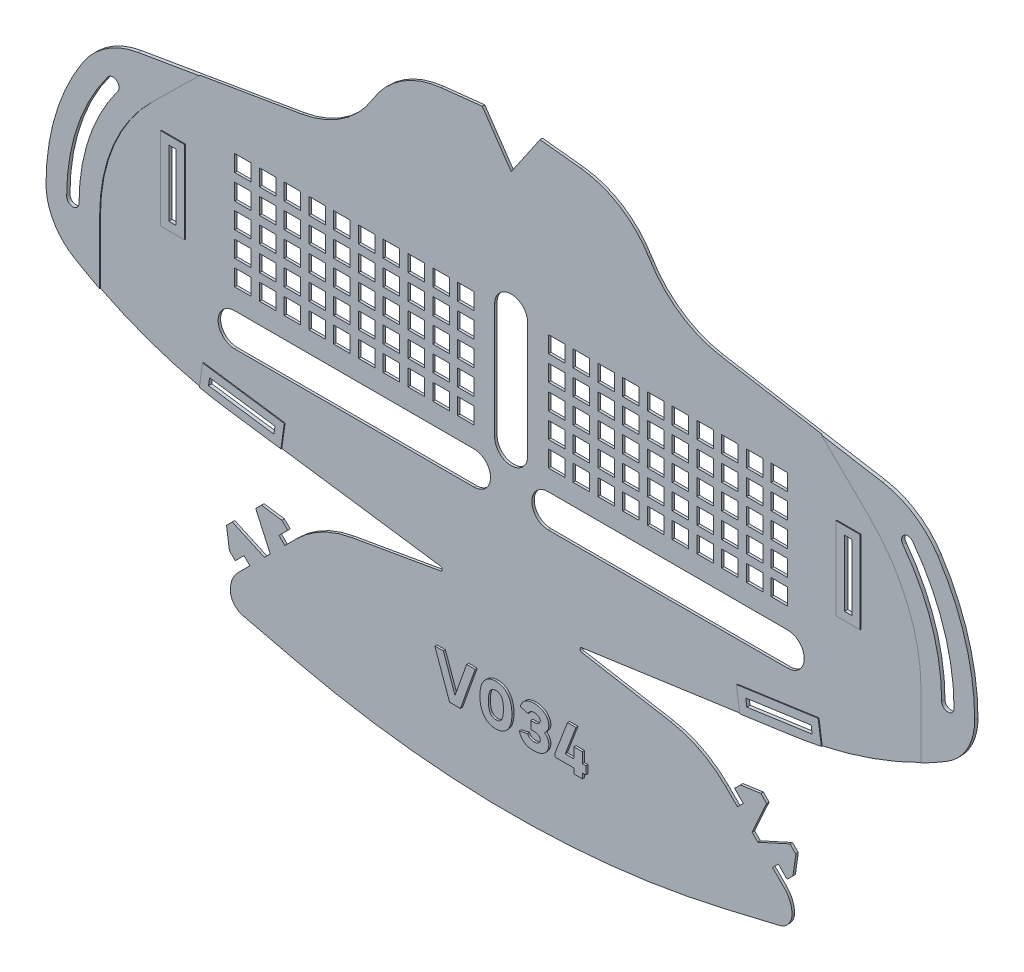
SolidWorks part; units mm, degrees
ref_plane "Front Plane" through (0, 0, 0) normal (0, 0, 1) x (1, 0, 0)
ref_plane "Top Plane" through (0, 0, 0) normal (0, 1, 0) x (1, 0, 0)
ref_plane "Right Plane" through (0, 0, 0) normal (1, 0, 0) x (0, 0, -1)
sketch "Sketch1" plane through (0, 0, 0) normal (0, 0, 1) x (1, 0, 0)
  line L0 (0, 0) -> (0, -145) construction
  line L1 (-14, -102) -> (14, -102) construction
  line L2 (-112.5, -69) -> (112.5, -69) construction
  line L3 (0, -10.2352) -> (-7, 0)
  line L4 (0, -10.2352) -> (7, 0)
  line L5 (7, 0) -> (16.9419, -1.0768)
  line L6 (-90.1804, -30.1909) -> (-50.7439, -23.5)
  line L7 (90.1804, -30.1909) -> (50.7439, -23.5)
  line L8 (-14, -102) -> (-68.2662, -94.2919)
  line L9 (-7, 0) -> (-16.9419, -1.0768)
  line L10 (14, -102) -> (68.2662, -94.2919)
  line L11 (-103.5977, -39) -> (-103.5977, -69) construction
  line L12 (-14, -102) -> (-38.6266, -106.305)
  line L13 (-52, -113.2546) -> (-54.8283, -116.0832)
  line L14 (52, -113.2546) -> (54.8283, -116.0832)
  line L15 (14, -102) -> (38.6266, -106.305)
  line L16 (-54.8283, -116.0832) -> (-56.2426, -114.669)
  line L17 (-56.2426, -114.669) -> (-54.1214, -112.5476)
  line L18 (-54.1214, -112.5476) -> (-55.5356, -111.1334)
  line L19 (-55.5356, -111.1334) -> (-60.4854, -110.4265)
  line L20 (-60.4854, -110.4265) -> (-68.9703, -118.9122)
  line L21 (-64.7275, -123.1546) -> (-63.3132, -124.5688)
  line L22 (-63.3132, -124.5688) -> (-66.1415, -127.3973)
  line L23 (-64.7275, -123.1546) -> (-66.8487, -125.2761)
  line L24 (-66.8487, -125.2761) -> (-68.263, -123.8619)
  line L25 (-68.9703, -118.9122) -> (-68.263, -123.8619)
  line L26 (68.9703, -118.9122) -> (68.263, -123.8619)
  line L27 (66.8487, -125.2761) -> (68.263, -123.8619)
  line L28 (64.7275, -123.1546) -> (66.8487, -125.2761)
  line L29 (63.3132, -124.5688) -> (66.1415, -127.3973)
  line L30 (64.7275, -123.1546) -> (63.3132, -124.5688)
  line L31 (60.4854, -110.4265) -> (68.9703, -118.9122)
  line L32 (55.5356, -111.1334) -> (60.4854, -110.4265)
  line L33 (54.1214, -112.5476) -> (55.5356, -111.1334)
  line L34 (56.2426, -114.669) -> (54.1214, -112.5476)
  line L35 (54.8283, -116.0832) -> (56.2426, -114.669)
  line L36 (-64.9691, -135.8852) -> (-52.4361, -138.8607)
  line L37 (64.9691, -135.8852) -> (52.4361, -138.8607)
  line L38 (-68.9703, -118.9122) -> (-64.7275, -123.1546) construction
  line L39 (-60.4854, -110.4265) -> (-56.2426, -114.669) construction
  arc A0 (-16.9419, -1.0768) -> (-33.4614, -11.6696) centre (-14.5729, -22.9489) ccw
  arc A1 (-33.4614, -11.6696) -> (-50.7439, -23.5) centre (-54.9257, 1.1478) cw
  arc A2 (-103.5977, -39) -> (-90.1804, -30.1909) centre (-86.8349, -49.9091) cw
  arc A3 (-112.5, -69) -> (-103.5977, -39) centre (-57.5, -69) cw
  arc A4 (112.5, -69) -> (103.5977, -39) centre (57.5, -69) ccw
  arc A5 (103.5977, -39) -> (90.1804, -30.1909) centre (86.8349, -49.9091) ccw
  arc A6 (16.9419, -1.0768) -> (33.4614, -11.6696) centre (14.5729, -22.9489) cw
  arc A7 (33.4614, -11.6696) -> (50.7439, -23.5) centre (54.9257, 1.1478) ccw
  arc A8 (-112.5, -69) -> (-105.7111, -81) centre (-98.5, -69) ccw
  arc A9 (-105.7111, -81) -> (-68.2662, -94.2919) centre (-54.2032, 4.7143) ccw
  arc A10 (112.5, -69) -> (105.7111, -81) centre (98.5, -69) cw
  arc A11 (105.7111, -81) -> (68.2662, -94.2919) centre (54.2032, 4.7143) cw
  arc A12 (-38.6266, -106.305) -> (-52, -113.2546) centre (-34.3216, -130.9315) ccw
  arc A13 (38.6266, -106.305) -> (52, -113.2546) centre (34.3216, -130.9315) cw
  arc A14 (-66.1415, -127.3973) -> (-68.0451, -131.9933) centre (-61.5451, -131.9933) ccw
  arc A15 (-68.0451, -131.9933) -> (-64.9691, -135.8852) centre (-64.0451, -131.9933) ccw
  arc A16 (68.0451, -131.9933) -> (64.9691, -135.8852) centre (64.0451, -131.9933) cw
  arc A17 (66.1415, -127.3973) -> (68.0451, -131.9933) centre (61.5451, -131.9933) cw
  arc A19 (-52.4361, -138.8607) -> (0, -145) centre (0, 82) ccw
  arc A20 (52.4361, -138.8607) -> (0, -145) centre (0, 82) cw
  point P8 (0, -102)
  point P11 (0, -69)
  dimension "D5" = 55
  dimension "D11" = 20
  dimension "D13" = 25
  dimension "D16" = 14
  dimension "D15" = 22
  dimension "D18" = 100
  dimension "D22" = 25
  dimension "D31" = 6.5
  dimension "D32" = 4
  dimension "D34" = 227
  dimension "D1" = 145
  dimension "D2" = 28
  dimension "D3" = 43
  dimension "D4" = 76
  dimension "D6" = 225
  dimension "D7" = 14
  dimension "D8" = 12.4
  dimension "D9" = 10
  dimension "D10" = 30
  dimension "D12" = 40
  dimension "D14" = 45.5
  dimension "D17" = 12
  dimension "D19" = 18
  dimension "D20" = 25
  dimension "D21" = 4
  dimension "D23" = 38
  dimension "D24" = 2
  dimension "D25" = 3
  dimension "D26" = 2
  dimension "D27" = 18
  dimension "D29" = 8
  dimension "D30" = 4
extrude "Main Shape" add sketch "Sketch1" along normal blind 0.6
sketch "Sketch2" plane through (0, 0, 0.6) normal (0, 0, 1) x (1, 0, 0)
  line L0 (0, -55) -> (0, 55) construction
  arc A0 (-96.3, -39.9) -> (-106, -69) centre (-57.5, -69) ccw construction
  arc A1 (-97.5, -39) -> (-107.5, -69) centre (-57.5, -69) ccw
  arc A2 (-95.1, -40.8) -> (-104.5, -69) centre (-57.5, -69) ccw
  arc A3 (-95.1, -40.8) -> (-97.5, -39) centre (-96.3, -39.9) ccw
  arc A4 (-107.5, -69) -> (-104.5, -69) centre (-106, -69) ccw
  arc A6 (-103.5977, -39) -> (-112.5, -69) centre (-57.5, -69) ccw construction
  arc A7 (96.3, -39.9) -> (106, -69) centre (57.5, -69) cw construction
  arc A8 (97.5, -39) -> (107.5, -69) centre (57.5, -69) cw
  arc A9 (95.1, -40.8) -> (104.5, -69) centre (57.5, -69) cw
  arc A10 (95.1, -40.8) -> (97.5, -39) centre (96.3, -39.9) cw
  arc A11 (107.5, -69) -> (104.5, -69) centre (106, -69) cw
  point P3 (-103.5111, -53.663)
  point P19 (103.5111, -53.663)
  dimension "D1" = 5
  dimension "D2" = 1.5
extrude "Elastic Attachment Points" cut sketch "Sketch2" against normal through all
sketch "Sketch7" plane through (0, 0, 0.6) normal (0, 0, 1) x (1, 0, 0)
  line L0 (-99.5, -69) -> (-99.5, -84.4384)
  line L1 (-86.8939, -39) -> (-75.3319, -27.6717)
  line L2 (-50.7439, -23.5) -> (-90.1804, -30.1909) construction
  line L3 (-75.3319, -27.6717) -> (-90.1804, -30.1909)
  line L4 (0, -55) -> (0, 55) construction
  line L5 (75.3319, -27.6717) -> (90.1804, -30.1909)
  line L6 (86.8939, -39) -> (75.3319, -27.6717)
  line L7 (99.5, -69) -> (99.5, -84.4384)
  arc A0 (-99.5, -69) -> (-86.8939, -39) centre (-57.5, -69) cw
  arc A1 (-95.1, -40.8) -> (-104.5, -69) centre (-57.5, -69) ccw construction
  arc A2 (-105.7111, -81) -> (-68.2662, -94.2919) centre (-54.2032, 4.7143) ccw construction
  arc A3 (-112.5, -69) -> (-105.7111, -81) centre (-98.5, -69) ccw construction
  arc A4 (-103.5977, -39) -> (-112.5, -69) centre (-57.5, -69) ccw construction
  arc A5 (-90.1804, -30.1909) -> (-103.5977, -39) centre (-86.8349, -49.9091) ccw construction
  arc A6 (-105.7111, -81) -> (-99.5, -84.4384) centre (-54.2032, 4.7143) ccw
  arc A7 (-112.5, -69) -> (-105.7111, -81) centre (-98.5, -69) ccw
  arc A8 (-103.5977, -39) -> (-112.5, -69) centre (-57.5, -69) ccw
  arc A9 (-90.1804, -30.1909) -> (-103.5977, -39) centre (-86.8349, -49.9091) ccw
  arc A10 (90.1804, -30.1909) -> (103.5977, -39) centre (86.8349, -49.9091) cw
  arc A11 (103.5977, -39) -> (112.5, -69) centre (57.5, -69) cw
  arc A12 (112.5, -69) -> (105.7111, -81) centre (98.5, -69) cw
  arc A13 (105.7111, -81) -> (99.5, -84.4384) centre (54.2032, 4.7143) cw
  arc A14 (99.5, -69) -> (86.8939, -39) centre (57.5, -69) ccw
  arc A15 (-107.5, -69) -> (-104.5, -69) centre (-106, -69) ccw construction
  arc A16 (-95.1, -40.8) -> (-97.5, -39) centre (-96.3, -39.9) ccw construction
  arc A17 (-97.5, -39) -> (-107.5, -69) centre (-57.5, -69) ccw construction
  arc A18 (-107.5, -69) -> (-104.5, -69) centre (-106, -69) ccw
  arc A19 (-95.1, -40.8) -> (-97.5, -39) centre (-96.3, -39.9) ccw
  arc A20 (-95.1, -40.8) -> (-104.5, -69) centre (-57.5, -69) ccw
  arc A21 (-97.5, -39) -> (-107.5, -69) centre (-57.5, -69) ccw
  arc A22 (104.5, -69) -> (107.5, -69) centre (106, -69) ccw construction
  arc A23 (97.5, -39) -> (95.1, -40.8) centre (96.3, -39.9) ccw construction
  arc A24 (104.5, -69) -> (95.1, -40.8) centre (57.5, -69) ccw construction
  arc A25 (107.5, -69) -> (97.5, -39) centre (57.5, -69) ccw construction
  arc A26 (104.5, -69) -> (107.5, -69) centre (106, -69) ccw
  arc A27 (97.5, -39) -> (95.1, -40.8) centre (96.3, -39.9) ccw
  arc A28 (104.5, -69) -> (95.1, -40.8) centre (57.5, -69) ccw
  arc A29 (107.5, -69) -> (97.5, -39) centre (57.5, -69) ccw
  dimension "D1" = 5
extrude "Reinforced Attachment Points" add sketch "Sketch7" along normal blind 0.2
sketch "Sketch6" plane through (0, 0, 0.6) normal (0, 0, 1) x (1, 0, 0)
  line L0 (-73.1225, -91.5821) -> (-57.2815, -93.8322)
  line L1 (-57.2815, -93.8322) -> (-57.0283, -92.05)
  line L2 (-57.0283, -92.05) -> (-72.8693, -89.8)
  line L3 (-72.8693, -89.8) -> (-73.1225, -91.5821)
  line L4 (-68.2662, -94.2919) -> (-14, -102) construction
  line L5 (-64.9488, -90.925) -> (-65.202, -92.7071) construction
  line L13 (0, -0.44) -> (0, 0.44) construction
  line L14 (64.9488, -90.925) -> (65.202, -92.7071) construction
  line L15 (73.1225, -91.5821) -> (72.8693, -89.8)
  line L16 (57.0283, -92.05) -> (57.2815, -93.8322)
  line L22 (57.0283, -92.05) -> (72.8693, -89.8)
  line L24 (73.1225, -91.5821) -> (57.2815, -93.8322)
  dimension "D1" = 2
  dimension "D2" = 16
  dimension "D3" = 52
  dimension "D4" = 1.8
extrude "Tab Slits" cut sketch "Sketch6" against normal through all
sketch "Sketch9" plane through (0, 0, 0.6) normal (0, 0, 1) x (1, 0, 0)
  line L4 (-57.2815, -93.8322) -> (-57.0283, -92.05) construction
  line L5 (-73.1225, -91.5821) -> (-57.2815, -93.8322) construction
  line L6 (-72.8693, -89.8) -> (-73.1225, -91.5821) construction
  line L7 (-57.0283, -92.05) -> (-72.8693, -89.8) construction
  line L12 (-57.2815, -93.8322) -> (-57.0283, -92.05)
  line L13 (-73.1225, -91.5821) -> (-57.2815, -93.8322)
  line L14 (-72.8693, -89.8) -> (-73.1225, -91.5821)
  line L15 (-57.0283, -92.05) -> (-72.8693, -89.8)
  line L16 (-55.5826, -96.0935) -> (-54.767, -90.3512)
  line L17 (-68.2662, -94.2919) -> (-14, -102) construction
  line L18 (-54.767, -90.3512) -> (-74.5682, -87.5386)
  line L19 (-74.5682, -87.5386) -> (-75.3475, -93.0248)
  line L20 (-68.2662, -94.2919) -> (-55.5826, -96.0935)
  line L21 (0, -0.44) -> (0, 0.44) construction
  line L22 (68.2662, -94.2919) -> (55.5826, -96.0935)
  line L23 (74.5682, -87.5386) -> (75.3475, -93.0248)
  line L24 (54.767, -90.3512) -> (74.5682, -87.5386)
  line L25 (55.5826, -96.0935) -> (54.767, -90.3512)
  line L26 (57.0283, -92.05) -> (72.8693, -89.8)
  line L27 (72.8693, -89.8) -> (73.1225, -91.5821)
  line L28 (73.1225, -91.5821) -> (57.2815, -93.8322)
  line L29 (57.2815, -93.8322) -> (57.0283, -92.05)
  arc A0 (-99.5, -84.4384) -> (-68.2662, -94.2919) centre (-54.2032, 4.7143) ccw construction
  arc A1 (-75.3475, -93.0248) -> (-68.2662, -94.2919) centre (-54.2032, 4.7143) ccw
  arc A2 (75.3475, -93.0248) -> (68.2662, -94.2919) centre (54.2032, 4.7143) cw
  dimension "D1" = 2
  dimension "D2" = 2
  dimension "D3" = 2
extrude "Reinforced Tab Slits" add sketch "Sketch9" along normal blind 0.2
sketch "Sketch11" plane through (0, 0, 0.6) normal (0, 0, 1) x (1, 0, 0)
  line L0 (-67.5562, -117.4979) -> (-59.7778, -121.0331)
  line L1 (-60.4854, -110.4265) -> (-68.9703, -118.9122) construction
  line L2 (-59.7778, -121.0331) -> (-58.3637, -119.6188)
  line L3 (-58.3637, -119.6188) -> (-61.8996, -111.8408)
  line L4 (-61.8996, -111.8408) -> (-67.5562, -117.4979)
  line L6 (-58.3637, -119.6188) -> (-54.8283, -116.0832) construction
  line L7 (-59.7778, -121.0331) -> (-63.3132, -124.5688) construction
  line L10 (0, -0.44) -> (0, 0.44) construction
  line L11 (59.7778, -121.0331) -> (63.3132, -124.5688) construction
  line L12 (58.3637, -119.6188) -> (54.8283, -116.0832) construction
  line L13 (61.8996, -111.8408) -> (67.5562, -117.4979)
  line L14 (58.3637, -119.6188) -> (61.8996, -111.8408)
  line L15 (59.7778, -121.0331) -> (58.3637, -119.6188)
  line L16 (67.5562, -117.4979) -> (59.7778, -121.0331)
  dimension "D1" = 2
  dimension "D2" = 2
  dimension "D3" = 5
extrude "Tab Flex Relief" cut sketch "Sketch11" against normal through all both and the other way through all
sketch "Sketch3" plane through (0, 0, 0.6) normal (0, 0, 1) x (1, 0, 0)
  line L3 (0, -10.2352) -> (0, -145) construction
  line L4 (-106, -69) -> (-96.3, -69) construction
  line L5 (-96.3, -69) -> (-96.3, -39.9) construction
  line L6 (-13, -39.9) -> (-9, -39.9)
  line L9 (-13, -39.9) -> (-13, -43.9)
  line L12 (-13, -43.9) -> (-9, -43.9)
  line L15 (-9, -39.9) -> (-9, -43.9)
  line L427 (0, -39.9) -> (0, -67.9) construction
  line L428 (4, -39.9) -> (4, -67.9)
  line L429 (-4, -39.9) -> (-4, -67.9)
  line L430 (-19, -39.9) -> (-15, -39.9)
  line L431 (-19, -39.9) -> (-19, -43.9)
  line L432 (-19, -43.9) -> (-15, -43.9)
  line L433 (-15, -39.9) -> (-15, -43.9)
  line L434 (-25, -39.9) -> (-21, -39.9)
  line L435 (-25, -39.9) -> (-25, -43.9)
  line L436 (-25, -43.9) -> (-21, -43.9)
  line L437 (-21, -39.9) -> (-21, -43.9)
  line L438 (-31, -39.9) -> (-27, -39.9)
  line L439 (-31, -39.9) -> (-31, -43.9)
  line L440 (-31, -43.9) -> (-27, -43.9)
  line L441 (-27, -39.9) -> (-27, -43.9)
  line L442 (-37, -39.9) -> (-33, -39.9)
  line L443 (-37, -39.9) -> (-37, -43.9)
  line L444 (-67, -76.9) -> (-9, -76.9) construction
  line L445 (-67, -72.9) -> (-9, -72.9)
  line L446 (-67, -80.9) -> (-9, -80.9)
  line L447 (67, -76.9) -> (9, -76.9) construction
  line L448 (67, -72.9) -> (9, -72.9)
  line L449 (67, -80.9) -> (9, -80.9)
  line L452 (-37, -43.9) -> (-33, -43.9)
  line L453 (-33, -39.9) -> (-33, -43.9)
  line L454 (-43, -39.9) -> (-39, -39.9)
  line L457 (-43, -39.9) -> (-43, -43.9)
  line L458 (-43, -43.9) -> (-39, -43.9)
  line L459 (-39, -39.9) -> (-39, -43.9)
  line L460 (-49, -39.9) -> (-45, -39.9)
  line L461 (-49, -39.9) -> (-49, -43.9)
  line L462 (-49, -43.9) -> (-45, -43.9)
  line L463 (-45, -39.9) -> (-45, -43.9)
  line L464 (-55, -39.9) -> (-51, -39.9)
  line L465 (-55, -39.9) -> (-55, -43.9)
  line L466 (-55, -43.9) -> (-51, -43.9)
  line L467 (-51, -39.9) -> (-51, -43.9)
  line L468 (-61, -39.9) -> (-57, -39.9)
  line L469 (-61, -39.9) -> (-61, -43.9)
  line L470 (-61, -43.9) -> (-57, -43.9)
  line L471 (-57, -39.9) -> (-57, -43.9)
  line L472 (-67, -39.9) -> (-63, -39.9)
  line L473 (-67, -39.9) -> (-67, -43.9)
  line L474 (-67, -43.9) -> (-63, -43.9)
  line L475 (-63, -39.9) -> (-63, -43.9)
  line L476 (-19, -45.9) -> (-15, -45.9)
  line L477 (-19, -45.9) -> (-19, -49.9)
  line L478 (-19, -49.9) -> (-15, -49.9)
  line L479 (-15, -45.9) -> (-15, -49.9)
  line L480 (-25, -45.9) -> (-21, -45.9)
  line L481 (-25, -45.9) -> (-25, -49.9)
  line L482 (-25, -49.9) -> (-21, -49.9)
  line L483 (-21, -45.9) -> (-21, -49.9)
  line L484 (-31, -45.9) -> (-27, -45.9)
  line L485 (-31, -45.9) -> (-31, -49.9)
  line L486 (-31, -49.9) -> (-27, -49.9)
  line L487 (-27, -45.9) -> (-27, -49.9)
  line L488 (-37, -45.9) -> (-33, -45.9)
  line L489 (-37, -45.9) -> (-37, -49.9)
  line L490 (-37, -49.9) -> (-33, -49.9)
  line L491 (-33, -45.9) -> (-33, -49.9)
  line L492 (-43, -45.9) -> (-39, -45.9)
  line L493 (-43, -45.9) -> (-43, -49.9)
  line L494 (-43, -49.9) -> (-39, -49.9)
  line L495 (-39, -45.9) -> (-39, -49.9)
  line L496 (-49, -45.9) -> (-45, -45.9)
  line L497 (-49, -45.9) -> (-49, -49.9)
  line L498 (-49, -49.9) -> (-45, -49.9)
  line L499 (-45, -45.9) -> (-45, -49.9)
  line L500 (-55, -45.9) -> (-51, -45.9)
  line L501 (-55, -45.9) -> (-55, -49.9)
  line L502 (-55, -49.9) -> (-51, -49.9)
  line L503 (-51, -45.9) -> (-51, -49.9)
  line L504 (-61, -45.9) -> (-57, -45.9)
  line L505 (-61, -45.9) -> (-61, -49.9)
  line L506 (-61, -49.9) -> (-57, -49.9)
  line L507 (-57, -45.9) -> (-57, -49.9)
  line L508 (-67, -45.9) -> (-63, -45.9)
  line L509 (-67, -45.9) -> (-67, -49.9)
  line L510 (-67, -49.9) -> (-63, -49.9)
  line L511 (-63, -45.9) -> (-63, -49.9)
  line L512 (-19, -51.9) -> (-15, -51.9)
  line L513 (-19, -51.9) -> (-19, -55.9)
  line L514 (-19, -55.9) -> (-15, -55.9)
  line L515 (-15, -51.9) -> (-15, -55.9)
  line L516 (-25, -51.9) -> (-21, -51.9)
  line L517 (-25, -51.9) -> (-25, -55.9)
  line L518 (-25, -55.9) -> (-21, -55.9)
  line L519 (-21, -51.9) -> (-21, -55.9)
  line L520 (-31, -51.9) -> (-27, -51.9)
  line L521 (-31, -51.9) -> (-31, -55.9)
  line L522 (-31, -55.9) -> (-27, -55.9)
  line L523 (-27, -51.9) -> (-27, -55.9)
  line L524 (-37, -51.9) -> (-33, -51.9)
  line L525 (-37, -51.9) -> (-37, -55.9)
  line L526 (-37, -55.9) -> (-33, -55.9)
  line L527 (-33, -51.9) -> (-33, -55.9)
  line L528 (-43, -51.9) -> (-39, -51.9)
  line L529 (-43, -51.9) -> (-43, -55.9)
  line L530 (-43, -55.9) -> (-39, -55.9)
  line L531 (-39, -51.9) -> (-39, -55.9)
  line L532 (-49, -51.9) -> (-45, -51.9)
  line L533 (-49, -51.9) -> (-49, -55.9)
  line L534 (-49, -55.9) -> (-45, -55.9)
  line L535 (-45, -51.9) -> (-45, -55.9)
  line L536 (-55, -51.9) -> (-51, -51.9)
  line L537 (-55, -51.9) -> (-55, -55.9)
  line L538 (-55, -55.9) -> (-51, -55.9)
  line L539 (-51, -51.9) -> (-51, -55.9)
  line L540 (-61, -51.9) -> (-57, -51.9)
  line L541 (-61, -51.9) -> (-61, -55.9)
  line L542 (-61, -55.9) -> (-57, -55.9)
  line L543 (-57, -51.9) -> (-57, -55.9)
  line L544 (-67, -51.9) -> (-63, -51.9)
  line L545 (-67, -51.9) -> (-67, -55.9)
  line L546 (-67, -55.9) -> (-63, -55.9)
  line L547 (-63, -51.9) -> (-63, -55.9)
  line L548 (-19, -57.9) -> (-15, -57.9)
  line L549 (-19, -57.9) -> (-19, -61.9)
  line L550 (-19, -61.9) -> (-15, -61.9)
  line L551 (-15, -57.9) -> (-15, -61.9)
  line L552 (-25, -57.9) -> (-21, -57.9)
  line L553 (-25, -57.9) -> (-25, -61.9)
  line L554 (-25, -61.9) -> (-21, -61.9)
  line L555 (-21, -57.9) -> (-21, -61.9)
  line L556 (-31, -57.9) -> (-27, -57.9)
  line L557 (-31, -57.9) -> (-31, -61.9)
  line L558 (-31, -61.9) -> (-27, -61.9)
  line L559 (-27, -57.9) -> (-27, -61.9)
  line L560 (-37, -57.9) -> (-33, -57.9)
  line L561 (-37, -57.9) -> (-37, -61.9)
  line L562 (-37, -61.9) -> (-33, -61.9)
  line L563 (-33, -57.9) -> (-33, -61.9)
  line L564 (-43, -57.9) -> (-39, -57.9)
  line L565 (-43, -57.9) -> (-43, -61.9)
  line L566 (-43, -61.9) -> (-39, -61.9)
  line L567 (-39, -57.9) -> (-39, -61.9)
  line L568 (-49, -57.9) -> (-45, -57.9)
  line L569 (-49, -57.9) -> (-49, -61.9)
  line L570 (-49, -61.9) -> (-45, -61.9)
  line L571 (-45, -57.9) -> (-45, -61.9)
  line L572 (-55, -57.9) -> (-51, -57.9)
  line L573 (-55, -57.9) -> (-55, -61.9)
  line L574 (-55, -61.9) -> (-51, -61.9)
  line L575 (-51, -57.9) -> (-51, -61.9)
  line L576 (-61, -57.9) -> (-57, -57.9)
  line L577 (-61, -57.9) -> (-61, -61.9)
  line L578 (-61, -61.9) -> (-57, -61.9)
  line L579 (-57, -57.9) -> (-57, -61.9)
  line L580 (-67, -57.9) -> (-63, -57.9)
  line L581 (-67, -57.9) -> (-67, -61.9)
  line L582 (-67, -61.9) -> (-63, -61.9)
  line L583 (-63, -57.9) -> (-63, -61.9)
  line L584 (-19, -63.9) -> (-15, -63.9)
  line L585 (-19, -63.9) -> (-19, -67.9)
  line L586 (-19, -67.9) -> (-15, -67.9)
  line L587 (-15, -63.9) -> (-15, -67.9)
  line L588 (-25, -63.9) -> (-21, -63.9)
  line L589 (-25, -63.9) -> (-25, -67.9)
  line L590 (-25, -67.9) -> (-21, -67.9)
  line L591 (-21, -63.9) -> (-21, -67.9)
  line L592 (-31, -63.9) -> (-27, -63.9)
  line L593 (-31, -63.9) -> (-31, -67.9)
  line L594 (-31, -67.9) -> (-27, -67.9)
  line L595 (-27, -63.9) -> (-27, -67.9)
  line L596 (-37, -63.9) -> (-33, -63.9)
  line L597 (-37, -63.9) -> (-37, -67.9)
  line L598 (-37, -67.9) -> (-33, -67.9)
  line L599 (-33, -63.9) -> (-33, -67.9)
  line L600 (-43, -63.9) -> (-39, -63.9)
  line L601 (-43, -63.9) -> (-43, -67.9)
  line L602 (-43, -67.9) -> (-39, -67.9)
  line L603 (-39, -63.9) -> (-39, -67.9)
  line L604 (-49, -63.9) -> (-45, -63.9)
  line L605 (-49, -63.9) -> (-49, -67.9)
  line L606 (-49, -67.9) -> (-45, -67.9)
  line L607 (-45, -63.9) -> (-45, -67.9)
  line L608 (-55, -63.9) -> (-51, -63.9)
  line L609 (-55, -63.9) -> (-55, -67.9)
  line L610 (-55, -67.9) -> (-51, -67.9)
  line L611 (-51, -63.9) -> (-51, -67.9)
  line L612 (-61, -63.9) -> (-57, -63.9)
  line L613 (-61, -63.9) -> (-61, -67.9)
  line L614 (-61, -67.9) -> (-57, -67.9)
  line L615 (-57, -63.9) -> (-57, -67.9)
  line L616 (-67, -63.9) -> (-63, -63.9)
  line L617 (-67, -63.9) -> (-67, -67.9)
  line L618 (-67, -67.9) -> (-63, -67.9)
  line L619 (-63, -63.9) -> (-63, -67.9)
  line L620 (-13, -45.9) -> (-9, -45.9)
  line L621 (-13, -45.9) -> (-13, -49.9)
  line L622 (-13, -49.9) -> (-9, -49.9)
  line L623 (-9, -45.9) -> (-9, -49.9)
  line L624 (-13, -51.9) -> (-9, -51.9)
  line L625 (-13, -51.9) -> (-13, -55.9)
  line L626 (-13, -55.9) -> (-9, -55.9)
  line L627 (-9, -51.9) -> (-9, -55.9)
  line L628 (-13, -57.9) -> (-9, -57.9)
  line L629 (-13, -57.9) -> (-13, -61.9)
  line L630 (-13, -61.9) -> (-9, -61.9)
  line L631 (-9, -57.9) -> (-9, -61.9)
  line L632 (-13, -63.9) -> (-9, -63.9)
  line L633 (-13, -63.9) -> (-13, -67.9)
  line L634 (-13, -67.9) -> (-9, -67.9)
  line L635 (-9, -63.9) -> (-9, -67.9)
  line L636 (9, -63.9) -> (9, -67.9)
  line L637 (13, -67.9) -> (9, -67.9)
  line L638 (13, -63.9) -> (13, -67.9)
  line L639 (13, -63.9) -> (9, -63.9)
  line L640 (9, -57.9) -> (9, -61.9)
  line L641 (13, -61.9) -> (9, -61.9)
  line L642 (13, -57.9) -> (13, -61.9)
  line L643 (13, -57.9) -> (9, -57.9)
  line L644 (9, -51.9) -> (9, -55.9)
  line L645 (13, -55.9) -> (9, -55.9)
  line L646 (13, -51.9) -> (13, -55.9)
  line L647 (13, -51.9) -> (9, -51.9)
  line L648 (9, -45.9) -> (9, -49.9)
  line L649 (13, -49.9) -> (9, -49.9)
  line L650 (13, -45.9) -> (13, -49.9)
  line L651 (13, -45.9) -> (9, -45.9)
  line L652 (63, -63.9) -> (63, -67.9)
  line L653 (67, -67.9) -> (63, -67.9)
  line L654 (67, -63.9) -> (67, -67.9)
  line L655 (67, -63.9) -> (63, -63.9)
  line L656 (57, -63.9) -> (57, -67.9)
  line L657 (61, -67.9) -> (57, -67.9)
  line L658 (61, -63.9) -> (61, -67.9)
  line L659 (61, -63.9) -> (57, -63.9)
  line L660 (51, -63.9) -> (51, -67.9)
  line L661 (55, -67.9) -> (51, -67.9)
  line L662 (55, -63.9) -> (55, -67.9)
  line L663 (55, -63.9) -> (51, -63.9)
  line L664 (45, -63.9) -> (45, -67.9)
  line L665 (49, -67.9) -> (45, -67.9)
  line L666 (49, -63.9) -> (49, -67.9)
  line L667 (49, -63.9) -> (45, -63.9)
  line L668 (39, -63.9) -> (39, -67.9)
  line L669 (43, -67.9) -> (39, -67.9)
  line L670 (43, -63.9) -> (43, -67.9)
  line L671 (43, -63.9) -> (39, -63.9)
  line L672 (33, -63.9) -> (33, -67.9)
  line L673 (37, -67.9) -> (33, -67.9)
  line L674 (37, -63.9) -> (37, -67.9)
  line L675 (37, -63.9) -> (33, -63.9)
  line L676 (27, -63.9) -> (27, -67.9)
  line L677 (31, -67.9) -> (27, -67.9)
  line L678 (31, -63.9) -> (31, -67.9)
  line L679 (31, -63.9) -> (27, -63.9)
  line L680 (21, -63.9) -> (21, -67.9)
  line L681 (25, -67.9) -> (21, -67.9)
  line L682 (25, -63.9) -> (25, -67.9)
  line L683 (25, -63.9) -> (21, -63.9)
  line L684 (15, -63.9) -> (15, -67.9)
  line L685 (19, -67.9) -> (15, -67.9)
  line L686 (19, -63.9) -> (19, -67.9)
  line L687 (19, -63.9) -> (15, -63.9)
  line L688 (63, -57.9) -> (63, -61.9)
  line L689 (67, -61.9) -> (63, -61.9)
  line L690 (67, -57.9) -> (67, -61.9)
  line L691 (67, -57.9) -> (63, -57.9)
  line L692 (57, -57.9) -> (57, -61.9)
  line L693 (61, -61.9) -> (57, -61.9)
  line L694 (61, -57.9) -> (61, -61.9)
  line L695 (61, -57.9) -> (57, -57.9)
  line L696 (51, -57.9) -> (51, -61.9)
  line L697 (55, -61.9) -> (51, -61.9)
  line L698 (55, -57.9) -> (55, -61.9)
  line L699 (55, -57.9) -> (51, -57.9)
  line L700 (45, -57.9) -> (45, -61.9)
  line L701 (49, -61.9) -> (45, -61.9)
  line L702 (49, -57.9) -> (49, -61.9)
  line L703 (49, -57.9) -> (45, -57.9)
  line L704 (39, -57.9) -> (39, -61.9)
  line L705 (43, -61.9) -> (39, -61.9)
  line L706 (43, -57.9) -> (43, -61.9)
  line L707 (43, -57.9) -> (39, -57.9)
  line L708 (33, -57.9) -> (33, -61.9)
  line L709 (37, -61.9) -> (33, -61.9)
  line L710 (37, -57.9) -> (37, -61.9)
  line L711 (37, -57.9) -> (33, -57.9)
  line L712 (27, -57.9) -> (27, -61.9)
  line L713 (31, -61.9) -> (27, -61.9)
  line L714 (31, -57.9) -> (31, -61.9)
  line L715 (31, -57.9) -> (27, -57.9)
  line L716 (21, -57.9) -> (21, -61.9)
  line L717 (25, -61.9) -> (21, -61.9)
  line L718 (25, -57.9) -> (25, -61.9)
  line L719 (25, -57.9) -> (21, -57.9)
  line L720 (15, -57.9) -> (15, -61.9)
  line L721 (19, -61.9) -> (15, -61.9)
  line L722 (19, -57.9) -> (19, -61.9)
  line L723 (19, -57.9) -> (15, -57.9)
  line L724 (63, -51.9) -> (63, -55.9)
  line L725 (67, -55.9) -> (63, -55.9)
  line L726 (67, -51.9) -> (67, -55.9)
  line L727 (67, -51.9) -> (63, -51.9)
  line L728 (57, -51.9) -> (57, -55.9)
  line L729 (61, -55.9) -> (57, -55.9)
  line L730 (61, -51.9) -> (61, -55.9)
  line L731 (61, -51.9) -> (57, -51.9)
  line L732 (51, -51.9) -> (51, -55.9)
  line L733 (55, -55.9) -> (51, -55.9)
  line L734 (55, -51.9) -> (55, -55.9)
  line L735 (55, -51.9) -> (51, -51.9)
  line L736 (45, -51.9) -> (45, -55.9)
  line L737 (49, -55.9) -> (45, -55.9)
  line L738 (49, -51.9) -> (49, -55.9)
  line L739 (49, -51.9) -> (45, -51.9)
  line L740 (39, -51.9) -> (39, -55.9)
  line L741 (43, -55.9) -> (39, -55.9)
  line L742 (43, -51.9) -> (43, -55.9)
  line L743 (43, -51.9) -> (39, -51.9)
  line L744 (33, -51.9) -> (33, -55.9)
  line L745 (37, -55.9) -> (33, -55.9)
  line L746 (37, -51.9) -> (37, -55.9)
  line L747 (37, -51.9) -> (33, -51.9)
  line L748 (27, -51.9) -> (27, -55.9)
  line L749 (31, -55.9) -> (27, -55.9)
  line L750 (31, -51.9) -> (31, -55.9)
  line L751 (31, -51.9) -> (27, -51.9)
  line L752 (21, -51.9) -> (21, -55.9)
  line L753 (25, -55.9) -> (21, -55.9)
  line L754 (25, -51.9) -> (25, -55.9)
  line L755 (25, -51.9) -> (21, -51.9)
  line L756 (15, -51.9) -> (15, -55.9)
  line L757 (19, -55.9) -> (15, -55.9)
  line L758 (19, -51.9) -> (19, -55.9)
  line L759 (19, -51.9) -> (15, -51.9)
  line L760 (63, -45.9) -> (63, -49.9)
  line L761 (67, -49.9) -> (63, -49.9)
  line L762 (67, -45.9) -> (67, -49.9)
  line L763 (67, -45.9) -> (63, -45.9)
  line L764 (57, -45.9) -> (57, -49.9)
  line L765 (61, -49.9) -> (57, -49.9)
  line L766 (61, -45.9) -> (61, -49.9)
  line L767 (61, -45.9) -> (57, -45.9)
  line L768 (51, -45.9) -> (51, -49.9)
  line L769 (55, -49.9) -> (51, -49.9)
  line L770 (55, -45.9) -> (55, -49.9)
  line L771 (55, -45.9) -> (51, -45.9)
  line L772 (45, -45.9) -> (45, -49.9)
  line L773 (49, -49.9) -> (45, -49.9)
  line L774 (49, -45.9) -> (49, -49.9)
  line L775 (49, -45.9) -> (45, -45.9)
  line L776 (39, -45.9) -> (39, -49.9)
  line L777 (43, -49.9) -> (39, -49.9)
  line L778 (43, -45.9) -> (43, -49.9)
  line L779 (43, -45.9) -> (39, -45.9)
  line L780 (33, -45.9) -> (33, -49.9)
  line L781 (37, -49.9) -> (33, -49.9)
  line L782 (37, -45.9) -> (37, -49.9)
  line L783 (37, -45.9) -> (33, -45.9)
  line L784 (27, -45.9) -> (27, -49.9)
  line L785 (31, -49.9) -> (27, -49.9)
  line L786 (31, -45.9) -> (31, -49.9)
  line L787 (31, -45.9) -> (27, -45.9)
  line L788 (21, -45.9) -> (21, -49.9)
  line L789 (25, -49.9) -> (21, -49.9)
  line L790 (25, -45.9) -> (25, -49.9)
  line L791 (25, -45.9) -> (21, -45.9)
  line L792 (15, -45.9) -> (15, -49.9)
  line L793 (19, -49.9) -> (15, -49.9)
  line L794 (19, -45.9) -> (19, -49.9)
  line L795 (19, -45.9) -> (15, -45.9)
  line L796 (63, -39.9) -> (63, -43.9)
  line L797 (67, -43.9) -> (63, -43.9)
  line L798 (67, -39.9) -> (67, -43.9)
  line L799 (67, -39.9) -> (63, -39.9)
  line L800 (57, -39.9) -> (57, -43.9)
  line L801 (61, -43.9) -> (57, -43.9)
  line L802 (61, -39.9) -> (61, -43.9)
  line L803 (61, -39.9) -> (57, -39.9)
  line L804 (51, -39.9) -> (51, -43.9)
  line L805 (55, -43.9) -> (51, -43.9)
  line L806 (55, -39.9) -> (55, -43.9)
  line L807 (55, -39.9) -> (51, -39.9)
  line L808 (45, -39.9) -> (45, -43.9)
  line L809 (49, -43.9) -> (45, -43.9)
  line L810 (49, -39.9) -> (49, -43.9)
  line L811 (49, -39.9) -> (45, -39.9)
  line L812 (39, -39.9) -> (39, -43.9)
  line L813 (43, -43.9) -> (39, -43.9)
  line L814 (43, -39.9) -> (43, -43.9)
  line L815 (43, -39.9) -> (39, -39.9)
  line L816 (33, -39.9) -> (33, -43.9)
  line L817 (37, -43.9) -> (33, -43.9)
  line L818 (37, -39.9) -> (37, -43.9)
  line L819 (37, -39.9) -> (33, -39.9)
  line L820 (27, -39.9) -> (27, -43.9)
  line L821 (31, -43.9) -> (27, -43.9)
  line L822 (31, -39.9) -> (31, -43.9)
  line L823 (31, -39.9) -> (27, -39.9)
  line L824 (21, -39.9) -> (21, -43.9)
  line L825 (25, -43.9) -> (21, -43.9)
  line L826 (25, -39.9) -> (25, -43.9)
  line L827 (25, -39.9) -> (21, -39.9)
  line L828 (15, -39.9) -> (15, -43.9)
  line L829 (19, -43.9) -> (15, -43.9)
  line L830 (19, -39.9) -> (19, -43.9)
  line L831 (19, -39.9) -> (15, -39.9)
  line L832 (9, -39.9) -> (9, -43.9)
  line L833 (13, -43.9) -> (9, -43.9)
  line L834 (13, -39.9) -> (13, -43.9)
  line L835 (13, -39.9) -> (9, -39.9)
  arc A2 (-52.4361, -138.8607) -> (52.4361, -138.8607) centre (0, 82) ccw construction
  arc A21 (4, -39.9) -> (-4, -39.9) centre (0, -39.9) ccw
  arc A22 (-4, -67.9) -> (4, -67.9) centre (0, -67.9) ccw
  arc A23 (-67, -72.9) -> (-67, -80.9) centre (-67, -76.9) ccw
  arc A24 (-9, -80.9) -> (-9, -72.9) centre (-9, -76.9) ccw
  arc A25 (67, -72.9) -> (67, -80.9) centre (67, -76.9) cw
  arc A26 (9, -80.9) -> (9, -72.9) centre (9, -76.9) cw
  point P4 (-38, -76.9)
  point P414 (0, -53.9)
  point P426 (0, 0)
  point P427 (0, 0)
  point P430 (38, -76.9)
  dimension "D2" = 4
  dimension "D3" = 5
  dimension "D4" = 5
  dimension "D5" = 28
  dimension "D7" = 2
  dimension "D9" = 5
  dimension "D10" = 8
  dimension "D8" = 8
  dimension "D6" = 10
extrude "Breathing Slits" cut sketch "Sketch3" against normal through all
sketch "Sketch8" plane through (0, 0, 0.6) normal (0, 0, 1) x (1, 0, 0)
  line L0 (-67.0266, -128.5) -> (67.0266, -128.5) construction
  line L1 (0, -10.2352) -> (0, -145) construction
  arc A0 (-52.4361, -138.8607) -> (52.4361, -138.8607) centre (0, 82) ccw construction
  arc A1 (-66.1415, -127.3973) -> (-68.0451, -131.9933) centre (-61.5451, -131.9933) ccw construction
  text T0 "<b>V034</b>" font "Double Porter 3" height 10
  point P9 (0, -128.5)
  dimension "D2" = 16.5
extrude "Version Number" add sketch "Sketch8" along normal blind 0.5
fillet "Fillet1" radius 0.5 2 edges at (-14, -102, 0.3) (14, -102, 0.3)
sketch "Sketch12" plane through (0, 0, 0.6) normal (0, 0, 1) x (1, 0, 0)
  line L2 (-82.7459, -45.9) -> (-80.9459, -45.9)
  line L3 (-82.7459, -45.9) -> (-82.7459, -61.9)
  line L4 (-82.7459, -61.9) -> (-80.9459, -61.9)
  line L5 (-80.9459, -45.9) -> (-80.9459, -61.9)
  line L6 (0, -10.2352) -> (0, -145) construction
  line L7 (-67, -51.9) -> (-67, -55.9) construction
  line L8 (-67, -53.9) -> (-96.6917, -53.9) construction
  line L9 (80.9459, -45.9) -> (80.9459, -61.9)
  line L10 (82.7459, -61.9) -> (80.9459, -61.9)
  line L11 (82.7459, -45.9) -> (82.7459, -61.9)
  line L12 (82.7459, -45.9) -> (80.9459, -45.9)
  arc A1 (-52.4361, -138.8607) -> (52.4361, -138.8607) centre (0, 82) ccw construction
  arc A2 (-86.8939, -39) -> (-99.5, -69) centre (-57.5, -69) ccw construction
  point P9 (-80.9459, -53.9)
  point P13 (-81.8459, -53.9)
  point P17 (-67, -53.9)
  point P23 (-81.8459, -61.9)
  dimension "D1" = 16
  dimension "D2" = 1.8
extrude "Tab Overlay Slit" cut sketch "Sketch12" against normal through all both and the other way through all
sketch "Sketch13" plane through (0, 0, 0.6) normal (0, 0, 1) x (1, 0, 0)
  line L0 (-80.9459, -61.9) -> (-82.7459, -61.9) construction
  line L1 (-84.7459, -43.9) -> (-78.9459, -43.9)
  line L2 (-84.7459, -43.9) -> (-84.7459, -63.9)
  line L3 (-84.7459, -63.9) -> (-78.9459, -63.9)
  line L4 (-78.9459, -43.9) -> (-78.9459, -63.9)
  line L5 (-82.7459, -61.9) -> (-82.7459, -45.9) construction
  line L6 (-80.9459, -45.9) -> (-80.9459, -61.9) construction
  line L7 (-82.7459, -45.9) -> (-80.9459, -45.9) construction
  line L8 (-80.9459, -61.9) -> (-82.7459, -61.9)
  line L9 (-80.9459, -45.9) -> (-80.9459, -61.9)
  line L10 (-82.7459, -45.9) -> (-80.9459, -45.9)
  line L11 (-82.7459, -61.9) -> (-82.7459, -45.9)
  line L12 (0, -0.605) -> (0, 0.605) construction
  line L13 (82.7459, -61.9) -> (82.7459, -45.9)
  line L14 (82.7459, -45.9) -> (80.9459, -45.9)
  line L15 (80.9459, -45.9) -> (80.9459, -61.9)
  line L16 (80.9459, -61.9) -> (82.7459, -61.9)
  line L17 (78.9459, -43.9) -> (78.9459, -63.9)
  line L18 (84.7459, -63.9) -> (78.9459, -63.9)
  line L19 (84.7459, -43.9) -> (84.7459, -63.9)
  line L20 (84.7459, -43.9) -> (78.9459, -43.9)
  point P8 (-81.8459, -63.9)
  point P9 (-81.8459, -61.9)
  point P10 (-82.7459, -53.9)
  point P11 (-84.7459, -53.9)
  dimension "D1" = 2
  dimension "D2" = 2
extrude "Tab Overlay Reinforcement" add sketch "Sketch13" along normal blind 0.2
